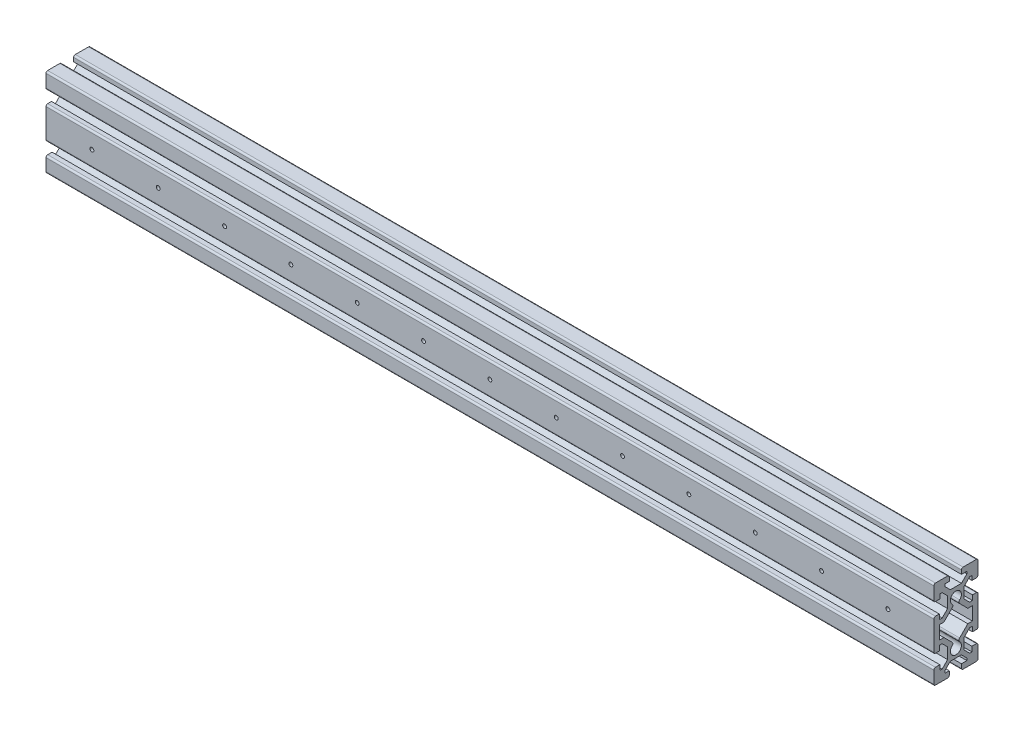
SolidWorks part; units mm, degrees
ref_plane "Piano frontale" through (0, 0, 0) normal (0, 0, 1) x (1, 0, 0)
ref_plane "Piano superiore" through (0, 0, 0) normal (0, 1, 0) x (1, 0, 0)
ref_plane "Piano destro" through (0, 0, 0) normal (1, 0, 0) x (0, 0, -1)
sketch "Schizzo1" plane through (0, 0, 0) normal (1, 0, 0) x (0, 0, -1)
  line L0 (20, 40.5) -> (5, 40.5) construction
  line L1 (18.5, -39.5) -> (6.5, -39.5)
  line L2 (-15, 6.0503) -> (-10.7929, 6.0503)
  line L3 (18.5, 40.5) -> (6.5, 40.5)
  line L4 (-20, -38) -> (-20, -27)
  line L7 (20, -39.5) -> (5, -39.5) construction
  line L21 (-12.4497, 10.0503) -> (-7.5, 15)
  line L22 (-20, -13) -> (-20, 13)
  line L23 (-18.5, 14.5) -> (-15, 14.5)
  line L24 (-14.5, 26) -> (-14.5, 29.9497)
  line L25 (-18.5, 26) -> (-14.5, 26)
  line L26 (-15, 10.0503) -> (-15, 14.5)
  line L27 (-12.4497, 10.0503) -> (-15, 10.0503)
  line L28 (-7.5, 15) -> (-7.5, 25)
  line L29 (-12.4497, 29.9497) -> (-14.5, 29.9497)
  line L30 (-12.4497, 29.9497) -> (-7.5, 25)
  line L32 (-12.4497, -29.9497) -> (-7.5, -25)
  line L33 (-12.4497, -29.9497) -> (-14.5, -29.9497)
  line L34 (-7.5, -15) -> (-7.5, -25)
  line L35 (-12.4497, -10.0503) -> (-15, -10.0503)
  line L36 (-15, -10.0503) -> (-15, -14.5)
  line L37 (-18.5, -25.5) -> (-14.5, -25.5)
  line L38 (-14.5, -25.5) -> (-14.5, -29.9497)
  line L39 (-18.5, -14.5) -> (-15, -14.5)
  line L40 (-9.9497, 35.5) -> (-6, 35.5)
  line L41 (-12.4497, -10.0503) -> (-7.5, -15)
  line L42 (20, -39.5) -> (5, -39.5) construction
  line L43 (-20, 27.5) -> (-20, 39)
  line L44 (-6, 39) -> (-6, 35.5)
  line L45 (5, 39) -> (5, 35.5)
  line L46 (9.9497, 33.4497) -> (5, 28.5)
  line L47 (-5, 28.5) -> (5, 28.5)
  line L48 (5, 35.5) -> (9.9497, 35.5)
  line L49 (-9.9497, 33.4497) -> (-9.9497, 35.5)
  line L50 (-9.9497, 33.4497) -> (-5, 28.5)
  line L51 (9.9497, 33.4497) -> (9.9497, 35.5)
  line L52 (9.9497, -32.4497) -> (9.9497, -34.5)
  line L53 (5, 40.5) -> (0, 40.5) construction
  line L54 (9.9497, 33.4497) -> (9.9497, 35.5)
  line L55 (0, -39.5) -> (5, -39.5) construction
  line L56 (9.9497, -32.4497) -> (9.9497, -34.5)
  line L57 (-9.9497, -32.4497) -> (-5, -27.5)
  line L58 (-9.9497, -32.4497) -> (-9.9497, -34.5)
  line L59 (5, -34.5) -> (9.9497, -34.5)
  line L60 (-5, -27.5) -> (5, -27.5)
  line L61 (9.9497, -32.4497) -> (5, -27.5)
  line L62 (5, -38) -> (5, -34.5)
  line L63 (-6, -38) -> (-6, -34.5)
  line L64 (-9.9497, -34.5) -> (-6, -34.5)
  line L65 (-7.5, 40.5) -> (-18.5, 40.5)
  line L66 (-7.5, -39.5) -> (-18.5, -39.5)
  line L70 (20, 27.5) -> (20, 39)
  line L71 (12.4497, -10.0503) -> (7.5, -15)
  line L72 (18.5, -14.5) -> (15, -14.5)
  line L73 (14.5, -25.5) -> (14.5, -29.9497)
  line L74 (18.5, -25.5) -> (14.5, -25.5)
  line L75 (15, -10.0503) -> (15, -14.5)
  line L76 (12.4497, -10.0503) -> (15, -10.0503)
  line L77 (7.5, -15) -> (7.5, -25)
  line L78 (12.4497, -29.9497) -> (14.5, -29.9497)
  line L79 (12.4497, -29.9497) -> (7.5, -25)
  line L80 (12.4497, 29.9497) -> (7.5, 25)
  line L81 (12.4497, 29.9497) -> (14.5, 29.9497)
  line L82 (7.5, 15) -> (7.5, 25)
  line L83 (12.4497, 10.0503) -> (15, 10.0503)
  line L84 (15, 10.0503) -> (15, 14.5)
  line L85 (18.5, 26) -> (14.5, 26)
  line L86 (14.5, 26) -> (14.5, 29.9497)
  line L87 (18.5, 14.5) -> (15, 14.5)
  line L88 (20, -13) -> (20, 13)
  line L89 (12.4497, 10.0503) -> (7.5, 15)
  line L90 (20, -38) -> (20, -27)
  line L91 (-15, 6.0503) -> (-15, -6.0503)
  line L92 (-15, 10.0503) -> (-15, 10)
  line L93 (-15, -10) -> (-15, -10.0503)
  line L94 (15, 10.0503) -> (15, 10)
  line L95 (-15, -6.0503) -> (-10.7929, -6.0503)
  line L96 (15, -10) -> (15, -10.0503)
  line L97 (15, 6.0503) -> (15, -6.0503)
  line L98 (-10.7929, 6.0503) -> (-3.3686, 13.4746)
  line L99 (10.7929, 6.0503) -> (3.3686, 13.4746)
  line L100 (10.7929, -6.0503) -> (3.3686, -13.4746)
  line L101 (-10.7929, -6.0503) -> (-3.3686, -13.4746)
  line L106 (10.7929, -6.0503) -> (15, -6.0503)
  line L107 (10.7929, 6.0503) -> (15, 6.0503)
  arc A0 (3.4163, 16.3491) -> (-3.4163, 16.3491) centre (0, 20) ccw
  arc A1 (-3.4163, -16.3491) -> (3.4163, -16.3491) centre (0, -20) ccw
  arc A2 (-3.3686, -13.4746) -> (-3.4163, -16.3491) centre (-4.7828, -14.8888) cw
  arc A3 (3.4163, -16.3491) -> (3.3686, -13.4746) centre (4.7828, -14.8888) cw
  arc A4 (3.4163, 16.3491) -> (3.3686, 13.4746) centre (4.7828, 14.8888) ccw
  arc A5 (-3.4163, 16.3491) -> (-3.3686, 13.4746) centre (-4.7828, 14.8888) cw
  arc A6 (-18.5, -25.5) -> (-20, -27) centre (-18.5, -27) ccw
  arc A7 (-7.5, -39.5) -> (-6, -38) centre (-7.5, -38) ccw
  arc A8 (6.5, -39.5) -> (5, -38) centre (6.5, -38) cw
  arc A9 (18.5, -25.5) -> (20, -27) centre (18.5, -27) cw
  arc A10 (20, -38) -> (18.5, -39.5) centre (18.5, -38) cw
  arc A11 (-18.5, -39.5) -> (-20, -38) centre (-18.5, -38) cw
  arc A12 (-20, 39) -> (-18.5, 40.5) centre (-18.5, 39) cw
  arc A13 (6.5, 40.5) -> (5, 39) centre (6.5, 39) ccw
  arc A14 (18.5, 40.5) -> (20, 39) centre (18.5, 39) cw
  arc A15 (20, 27.5) -> (18.5, 26) centre (18.5, 27.5) cw
  arc A16 (18.5, 14.5) -> (20, 13) centre (18.5, 13) cw
  arc A17 (20, -13) -> (18.5, -14.5) centre (18.5, -13) cw
  arc A18 (-18.5, -14.5) -> (-20, -13) centre (-18.5, -13) cw
  arc A19 (-20, 13) -> (-18.5, 14.5) centre (-18.5, 13) cw
  arc A20 (-18.5, 26) -> (-20, 27.5) centre (-18.5, 27.5) cw
  arc A21 (-7.5, 40.5) -> (-6, 39) centre (-7.5, 39) cw
  point P0 (0, 0)
  point P130 (-20, -25.5)
  point P166 (-20, -14.5)
  point P169 (-20, 14.5)
  point P172 (-20, 26)
  point P175 (-6, 40.5)
  dimension "D1" = 5
  dimension "D2" = 1.5
  dimension "D7" = 10
  dimension "D8" = 13.4746
  dimension "D3" = 20
  dimension "D4" = 6
  dimension "D5" = 9.9497
  dimension "D6" = 6.0503
  dimension "D9" = 25
  dimension "D10" = 14.5
  dimension "D11" = 15
  dimension "D12" = 14.5
  dimension "D13" = 25
  dimension "D14" = 29.9497
  dimension "D15" = 2
  dimension "D16" = 16.3491
  dimension "D18" = 26
  dimension "D20" = 14.5
  dimension "D21" = 15
  dimension "D22" = 20
  dimension "D25" = 35.5
  dimension "D28" = 10
  dimension "D37" = 25.5
  dimension "D42" = 39.5
extrude "Estrusione-Estrusione1" add sketch "Schizzo1" along normal blind 803 contours A21 L65 A12 L43 A20 L25 L24 L29 L30 L28 L21 L27 L26 L23 A19 L22 A18 L39 L36 L35 L41 L34 L32 L33 L38 L37 A6 L4 A11 L66 A7 L63 L64 L58 L57 L60 L61 L52 L59 L62 A8 L1 A10 L90 A9 L74 L73 region at (0, -38.6056, -12.5)
sketch "Schizzo2" plane through (0, 0, 20) normal (0, 0, 1) x (1, 0, 0)
  line L0 (0, 0) -> (803, 0) construction
  line L1 (0, -13) -> (0, 13) construction
  line L2 (803, -13) -> (803, 13) construction
  line L3 (401.5, 13) -> (401.5, -13) construction
  line L4 (803, 13) -> (0, 13) construction
  line L5 (803, -13) -> (0, -13) construction
  circle A0 centre (401.5, 0) radius 1.75
  circle A1 centre (461.5, 0) radius 1.75
  circle A2 centre (521.5, 0) radius 1.75
  circle A3 centre (581.5, 0) radius 1.75
  circle A4 centre (641.5, 0) radius 1.75
  circle A5 centre (701.5, 0) radius 1.75
  circle A6 centre (761.5, 0) radius 1.75
  circle A7 centre (41.5, 0) radius 1.75
  circle A8 centre (101.5, 0) radius 1.75
  circle A9 centre (161.5, 0) radius 1.75
  circle A10 centre (221.5, 0) radius 1.75
  circle A11 centre (281.5, 0) radius 1.75
  circle A12 centre (341.5, 0) radius 1.75
  dimension "D2" = 3.5
  dimension "D1" = 7
extrude "Taglio-Estrusione1" cut sketch "Schizzo2" against normal blind 10
